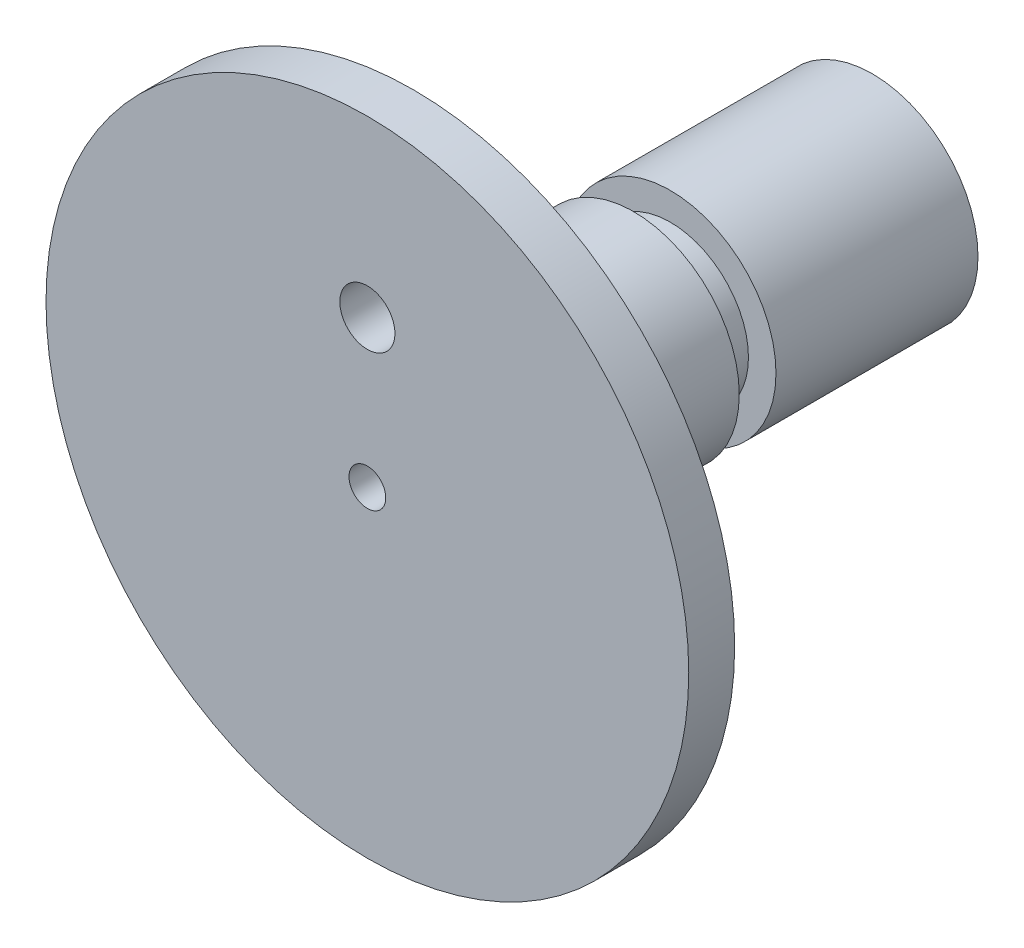
SolidWorks part; units mm, degrees
ref_plane "Alzado" through (0, 0, 0) normal (0, 0, 1) x (1, 0, 0)
ref_plane "Planta" through (0, 0, 0) normal (0, 1, 0) x (1, 0, 0)
ref_plane "Vista lateral" through (0, 0, 0) normal (1, 0, 0) x (0, 0, -1)
sketch "Croquis2" plane through (0, 0, 0) normal (0, 0, 1) x (1, 0, 0)
  circle A0 centre (0, 0) radius 17.5
  dimension "D1" = 35
extrude "Saliente-Extruir1" add sketch "Croquis2" along normal mid plane 2.5
sketch "Croquis3" plane through (0, 0, -1.25) normal (0, 0, -1) x (-1, 0, 0)
  line L0 (0, 7.5996) -> (0, -8.5454) construction
  line L1 (-1.95, 1.9391) -> (-1.95, -1.9391)
  line L2 (1.95, 1.9391) -> (1.95, -1.9391)
  circle A0 centre (0, 0) radius 2.75
  circle A1 centre (0, 0) radius 5.75
  dimension "D1" = 5.5
  dimension "D2" = 3
  dimension "D3" = 3.9
extrude "Saliente-Extruir2" add sketch "Croquis3" along normal blind 25 contours L0 A1 A0 | A1 L0 A0 | L1 A0 | L2 A0 region at (-2.818, 0, -1.25) region at (2.818, 0, -1.25) region at (-2.2744, 0, -1.25) region at (2.2744, 0, -1.25)
sketch "Croquis4" plane through (0, 0, 1.25) normal (0, 0, 1) x (1, 0, 0)
  circle A0 centre (0, 0) radius 1
  dimension "D1" = 2
extrude "Cortar-Extruir1" cut sketch "Croquis4" against normal blind 15
sketch "Croquis7" plane through (0, 0, 1.25) normal (0, 0, 1) x (1, 0, 0)
  line L0 (0, 0) -> (0, 8) construction
  circle A0 centre (0, 8) radius 1.5
  dimension "D1" = 3
  dimension "D2" = 8
extrude "Cortar-Extruir2" cut sketch "Croquis7" against normal blind 10
sketch "Croquis8" plane through (0, 0, 0) normal (0, 1, 0) x (1, 0, 0)
  line L0 (0, 0) -> (0, 24.7224) construction
  line L1 (5.75, 1.25) -> (5.75, 26.25) construction
  line L2 (5.75, 1.25) -> (5.75, 26.25) construction
  line L3 (17.5, 1.25) -> (-17.5, 1.25) construction
  line L4 (5.75, 15.25) -> (4.25, 15.25)
  line L5 (5.75, 15.25) -> (5.75, 13.25)
  line L6 (5.75, 13.25) -> (4.25, 13.25)
  line L7 (4.25, 15.25) -> (4.25, 13.25)
  line L9 (5.75, 9.25) -> (4.75, 9.25)
  line L10 (5.75, 9.25) -> (5.75, 7.25)
  line L11 (5.75, 7.25) -> (4.75, 7.25)
  line L12 (4.75, 9.25) -> (4.75, 7.25)
  dimension "D1" = 1.5
  dimension "D2" = 2
  dimension "D3" = 12
  dimension "D4" = 1
  dimension "D5" = 2
  dimension "D6" = 6
revolve "Cortar-Revolución1" cut sketch "Croquis8" angle 360 about L0
sketch "Croquis10" plane through (0, 0, 0) normal (0, 1, 0) x (1, 0, 0)
  line L0 (-5.75, 3.75) -> (-8.75, 1.25)
  line L1 (-5.75, 7.25) -> (-5.75, 1.25) construction
  line L2 (17.5, 1.25) -> (-17.5, 1.25) construction
  line L3 (-5.75, 3.75) -> (-5.75, 1.25)
  line L4 (-5.75, 1.25) -> (-8.75, 1.25)
  line L5 (0, 2.4411) -> (0, -2.2636) construction
  dimension "D1" = 3
  dimension "D2" = 2.5
revolve "Revolución1" add sketch "Croquis10" angle 235 about L5 other way angle 57
